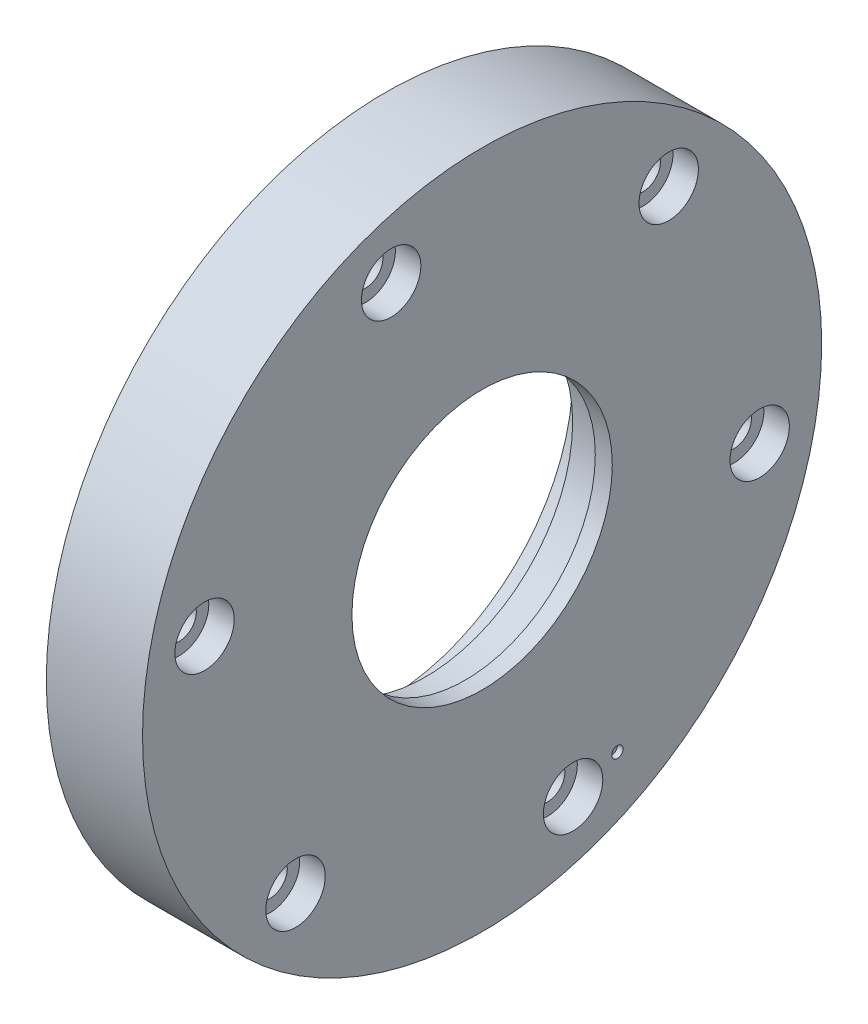
SolidWorks part; units mm, degrees
ref_plane "Front Plane" through (0, 0, 0) normal (0, 0, 1) x (1, 0, 0)
ref_plane "Top Plane" through (0, 0, 0) normal (0, 1, 0) x (1, 0, 0)
ref_plane "Right Plane" through (0, 0, 0) normal (1, 0, 0) x (0, 0, -1)
sketch "Sketch1" plane through (0, 0, 0) normal (0, 0, 1) x (1, 0, 0)
  line L0 (0, 0) -> (14, 0) construction
  line L1 (0, 60) -> (0, 33)
  line L2 (0, 33) -> (7, 33)
  line L3 (7, 33) -> (7, 26)
  line L4 (7, 26) -> (14, 26)
  line L5 (14, 26) -> (14, 23)
  line L6 (14, 23) -> (17, 23)
  line L7 (17, 23) -> (17, 60)
  line L8 (17, 60) -> (0, 60)
  dimension "D1" = 17
  dimension "D2" = 26
  dimension "D3" = 7
  dimension "D4" = 3
  dimension "D5" = 60
  dimension "D6" = 33
  dimension "D7" = 3
revolve "Revolve1" add sketch "Sketch1" angle 360 about L0
sketch "Sketch2" plane through (0, 0, 0) normal (-1, 0, 0) x (0, 0, 1)
  circle A0 centre (0, 0) radius 40 construction
  circle A1 centre (0, 40) radius 2.5
  circle A2 centre (15.3073, 36.9552) radius 2.5
  circle A3 centre (28.2843, 28.2843) radius 2.5
  circle A4 centre (36.9552, 15.3073) radius 2.5
  circle A5 centre (40, 0) radius 2.5
  circle A6 centre (36.9552, -15.3073) radius 2.5
  circle A7 centre (28.2843, -28.2843) radius 2.5
  circle A8 centre (15.3073, -36.9552) radius 2.5
  circle A9 centre (0, -40) radius 2.5
  circle A10 centre (-15.3073, -36.9552) radius 2.5
  circle A11 centre (-28.2843, -28.2843) radius 2.5
  circle A12 centre (-36.9552, -15.3073) radius 2.5
  circle A13 centre (-40, 0) radius 2.5
  circle A14 centre (-36.9552, 15.3073) radius 2.5
  circle A15 centre (-28.2843, 28.2843) radius 2.5
  circle A16 centre (-15.3073, 36.9552) radius 2.5
  point P37 (0, 0)
  dimension "D1" = 80
  dimension "D2" = 5
  dimension "D3" = 16
extrude "Cut-Extrude1" cut sketch "Sketch2" against normal blind 4
sketch "Sketch3" plane through (17, 0, 0) normal (1, 0, 0) x (0, 0, -1)
  circle A0 centre (49.0393, -9.7545) radius 3.05
  circle A1 centre (16.072, -47.3465) radius 3.05
  circle A2 centre (-32.9673, -37.592) radius 3.05
  circle A3 centre (-49.0393, 9.7545) radius 3.05
  circle A4 centre (-16.072, 47.3465) radius 3.05
  circle A5 centre (32.9673, 37.592) radius 3.05
  point P20 (0, 0)
  dimension "D2" = 6.1
  dimension "D1" = 6
extrude "Cut-Extrude4" cut sketch "Sketch3" against normal through all
sketch "Sketch4" plane through (17, 0, 0) normal (1, 0, 0) x (0, 0, -1)
  circle A0 centre (32.9673, 37.592) radius 5.25
  circle A1 centre (49.0393, -9.7545) radius 5.25
  circle A2 centre (16.072, -47.3465) radius 5.25
  circle A3 centre (-32.9673, -37.592) radius 5.25
  circle A4 centre (-49.0393, 9.7545) radius 5.25
  circle A5 centre (-16.072, 47.3465) radius 5.25
  point P20 (0, 0)
  dimension "D1" = 10.5
  dimension "D2" = 6
extrude "Cut-Extrude5" cut sketch "Sketch4" against normal blind 4.5
sketch "Sketch5" [suppressed] plane through (17, 0, 0) normal (1, 0, 0) x (0, 0, -1)
  line L0 (32.9673, 37.592) -> (0, 0) construction
  line L1 (0, 0) -> (41.6649, 14.1433) construction
  circle A0 centre (32.9673, 37.592) radius 3.3
  circle A1 centre (49.0393, -9.7545) radius 3.3
  circle A2 centre (16.072, -47.3465) radius 3.3
  circle A3 centre (-32.9673, -37.592) radius 3.3
  circle A4 centre (-49.0393, 9.7545) radius 3.3
  circle A5 centre (-16.072, 47.3465) radius 3.3
  circle A8 centre (0, 0) radius 44 construction
  circle A9 centre (41.6649, 14.1433) radius 3.3
  circle A10 centre (-8.584, -43.1546) radius 3.3
  circle A11 centre (-33.081, 29.0112) radius 3.3
  point P19 (0, 0)
  point P33 (0, 0)
  dimension "D1" = 6.6
  dimension "D4" = 88
  dimension "D5" = 30
  dimension "D2" = 6
  dimension "D3" = 3
extrude "Cut-Extrude6" [suppressed] cut sketch "Sketch5" against normal blind 10
chamfer "Chamfer1" [suppressed] distance 1 angle 45
sketch "Sketch6" plane through (17, 0, 0) normal (1, 0, 0) x (0, 0, -1)
  circle A0 centre (23.9053, -44.4252) radius 1
  dimension "D1" = 2
extrude "Cut-Extrude7" cut sketch "Sketch6" against normal blind 1
sketch "Sketch7" [suppressed] plane through (0, 0, 0) normal (-1, 0, 0) x (0, 0, 1)
  circle A0 centre (39.0864, -31.8954) radius 1
  dimension "D1" = 2
extrude "Cut-Extrude8" [suppressed] cut sketch "Sketch7" against normal blind 1
equation "\"R_ROLL\"= 5mm"
equation "\"D_SUN\"= 80mm"
equation "\"NUM_ROLL\"= 16"
equation "\"RHO\"= 1mm"
equation "\"D_SHAFT\"= 15mm"
equation "\"D_OUTPUT\"= 40mm"
equation "\"NUM_OUT\"= 6"
equation "\"R_OUT_ROLL\"= 5mm"
equation "\"D1@Sketch2\"=\"D_SUN\""
equation "\"D3@Sketch2\"=\"NUM_ROLL\""
